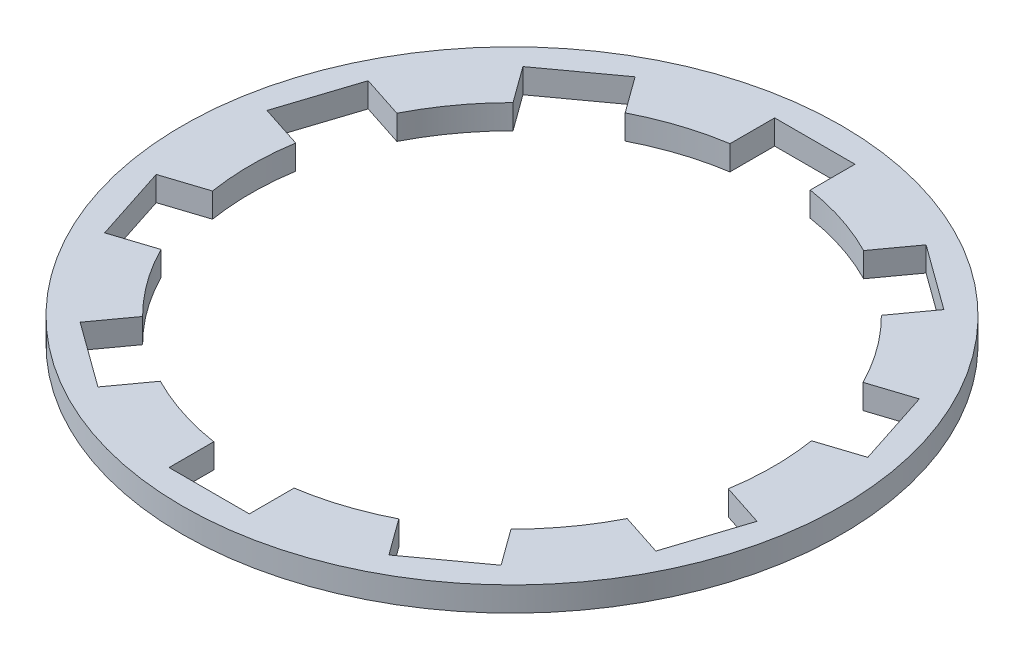
SolidWorks part; units mm, degrees
material "Plain Carbon Steel"
ref_plane "Front Plane" through (0, 0, 0) normal (0, 0, 1) x (1, 0, 0)
ref_plane "Top Plane" through (0, 0, 0) normal (0, 1, 0) x (1, 0, 0)
ref_plane "Right Plane" through (0, 0, 0) normal (1, 0, 0) x (0, 0, -1)
sketch "Sketch1" plane through (0, 0, 0) normal (0, 1, 0) x (1, 0, 0)
  circle A0 centre (0, 0) radius 7.5311
  circle A1 centre (0, 0) radius 5.969
  dimension "D1" = 15.0622
  dimension "D2" = 11.938
extrude "Boss-Extrude1" add sketch "Sketch1" along normal blind 0.5588
sketch "Sketch2" plane through (0, 0.5588, 0) normal (0, 1, 0) x (1, 0, 0)
  line L1 (0.9174, 5.0181) -> (-0.9174, 5.0181)
  line L2 (0.9174, 5.0181) -> (0.9174, 6.9199)
  line L3 (0.9174, 6.9199) -> (-0.9174, 6.9199)
  line L4 (-0.9174, 5.0181) -> (-0.9174, 6.9199)
  line L5 (0.9174, 5.0181) -> (-0.9174, 6.9199) construction
  line L6 (0.9174, 6.9199) -> (-0.9174, 5.0181) construction
  circle A0 centre (0, 0) radius 5.969 construction
  point P0 (0, 5.969)
extrude "Cut-Extrude1" cut sketch "Sketch2" against normal through all
pattern_circular "CirPattern1" count 10 over 360 about axis through (0, 0.5588, 0) along (0, -1, 0) of "Cut-Extrude1"
